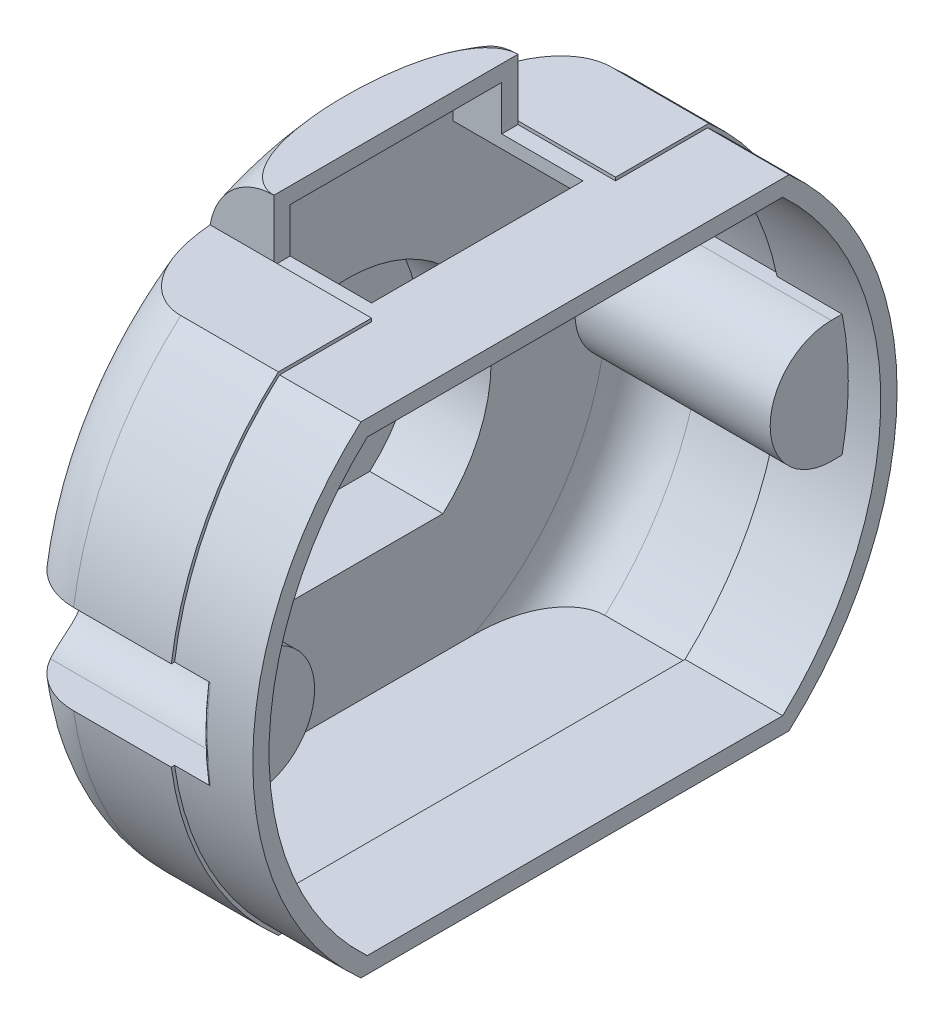
SolidWorks part; units mm, degrees
ref_plane "Alzado" through (0, 0, 0) normal (0, 0, 1) x (1, 0, 0)
ref_plane "Planta" through (0, 0, 0) normal (0, 1, 0) x (1, 0, 0)
ref_plane "Vista lateral" through (0, 0, 0) normal (1, 0, 0) x (0, 0, -1)
sketch "Croquis1" plane through (0, 0, 0) normal (1, 0, 0) x (0, 0, -1)
  circle A0 centre (0, 0) radius 4.925
extrude "Saliente-Extruir1" add sketch "Croquis1" along normal blind 2.25
sketch "Croquis2" plane through (2.25, 0, 0) normal (1, 0, 0) x (0, 0, -1)
  line L1 (-4.925, -3.8032) -> (4.925, -3.8032)
  line L2 (-4.925, -3.8032) -> (-4.925, 13.8968)
  line L3 (-4.925, 13.8968) -> (4.925, 13.8968)
  line L4 (4.925, -3.8032) -> (4.925, 13.8968)
  line L5 (-4.925, -3.8032) -> (4.925, 13.8968) construction
  line L6 (-4.925, 13.8968) -> (4.925, -3.8032) construction
  circle A0 centre (0, 0) radius 4.925 construction
  point P0 (0, -4.925)
extrude "Cortar-Extruir1" cut sketch "Croquis2" against normal blind 2.25 flip side to cut
sketch "Croquis3" plane through (2.25, 0, 0) normal (1, 0, 0) x (0, 0, -1)
  circle A0 centre (0, 0) radius 10
extrude "Saliente-Extruir2" add sketch "Croquis3" along normal blind 5
fillet "Redondeo1" radius 2 1 edges at (2.25, 0, -10)
fillet "Redondeo2" radius 0.5 2 edges at (0, -3.8032, 0) (0, 4.925, 0)
sketch "Croquis4" plane through (7.25, 0, 0) normal (1, 0, 0) x (0, 0, -1)
  line L0 (0, 7.5) -> (0, 9.2702) construction
  line L1 (-10, 7.5) -> (10, 7.5) construction
  line L2 (-10, 7.5) -> (-10, -7.5)
  line L3 (-10, -7.5) -> (10, -7.5)
  line L4 (10, 7.5) -> (10, -7.5)
  line L5 (-10, 7.5) -> (10, -7.5) construction
  line L6 (-10, -7.5) -> (10, 7.5) construction
  line L7 (0, 9.2702) -> (3.75, 9.2702)
  line L8 (3.75, 9.2702) -> (3.75, 7.5)
  line L9 (3.75, 7.5) -> (10, 7.5)
  line L10 (0, 9.2702) -> (-3.75, 9.2702)
  line L11 (-3.75, 9.2702) -> (-3.75, 7.5)
  line L12 (-3.75, 7.5) -> (-10, 7.5)
  circle A0 centre (0, 0) radius 10 construction
  point P0 (0, 0)
extrude "Cortar-Extruir2" cut sketch "Croquis4" against normal blind 5 flip side to cut
sketch "Croquis5" plane through (7.25, 0, 0) normal (1, 0, 0) x (0, 0, -1)
  line L0 (-6.6144, 7.5) -> (6.6144, 7.5) construction
  line L1 (6.6144, -7.5) -> (-6.6144, -7.5) construction
  line L2 (6.5765, -7.4) -> (-6.5765, -7.4)
  line L3 (-6.5765, 7.4) -> (6.5765, 7.4)
  arc A0 (-6.6144, 7.5) -> (-6.6144, -7.5) centre (0, 0) ccw construction
  arc A1 (6.6144, 7.5) -> (6.6144, -7.5) centre (0, 0) cw construction
  arc A2 (-6.5765, 7.4) -> (-6.5765, -7.4) centre (0, 0) ccw
  arc A3 (6.5765, 7.4) -> (6.5765, -7.4) centre (0, 0) cw
  dimension "D1" = 0.1
extrude "Saliente-Extruir3" add sketch "Croquis5" along normal blind 2.5
sketch "Croquis6" plane through (9.75, 0, 0) normal (1, 0, 0) x (0, 0, -1)
  line L0 (-10, 0) -> (-8.875, 0) construction
  line L1 (-8.875, 0) -> (-8.875, 1.375) construction
  line L2 (-8.875, 0) -> (-8.875, -1.375) construction
  line L3 (-8.875, 1.375) -> (-10, 1.375)
  line L4 (-10, 1.375) -> (-10, -1.375)
  line L5 (-10, -1.375) -> (-8.875, -1.375)
  line L6 (0, 7.4) -> (0, -7.4) construction
  line L7 (6.5765, 7.4) -> (-6.5765, 7.4) construction
  line L8 (-6.5765, -7.4) -> (6.5765, -7.4) construction
  line L9 (10, 1.375) -> (10, -1.375)
  line L10 (10, -1.375) -> (8.875, -1.375)
  line L11 (8.875, 1.375) -> (10, 1.375)
  arc A0 (-6.6144, 7.5) -> (-6.6144, -7.5) centre (0, 0) ccw construction
  arc A1 (-8.875, 1.375) -> (-8.875, -1.375) centre (-8.875, 0) cw
  arc A2 (8.875, 1.375) -> (8.875, -1.375) centre (8.875, 0) ccw
extrude "Cortar-Extruir3" cut sketch "Croquis6" against normal up to next from offset 1.5 offset against normal yes
shell "Vaciado1" thickness 0.5 removed face at (9.75, 0, 0)
sketch "Croquis8" plane through (0, 0, 0) normal (-1, 0, 0) x (0, 0, 1)
  circle A0 centre (0, 0) radius 1
extrude "Cortar-Extruir4" cut sketch "Croquis8" against normal up to next
sketch "Croquis9" plane through (7.25, 0, 0) normal (1, 0, 0) x (0, 0, -1)
  line L0 (6.5765, 7.4) -> (-6.5765, 7.4) construction
  line L1 (-3.75, 9.2702) -> (3.75, 9.2702)
  line L2 (-3.75, 9.2702) -> (-3.75, 7.4)
  line L3 (-3.75, 7.4) -> (3.75, 7.4)
  line L4 (3.75, 9.2702) -> (3.75, 7.4)
extrude "Cortar-Extruir5" cut sketch "Croquis9" against normal blind 3
fillet "Redondeo3" radius 0.1 2 edges at (8.25, 0, -9.9) (8.25, 0, 9.9)
